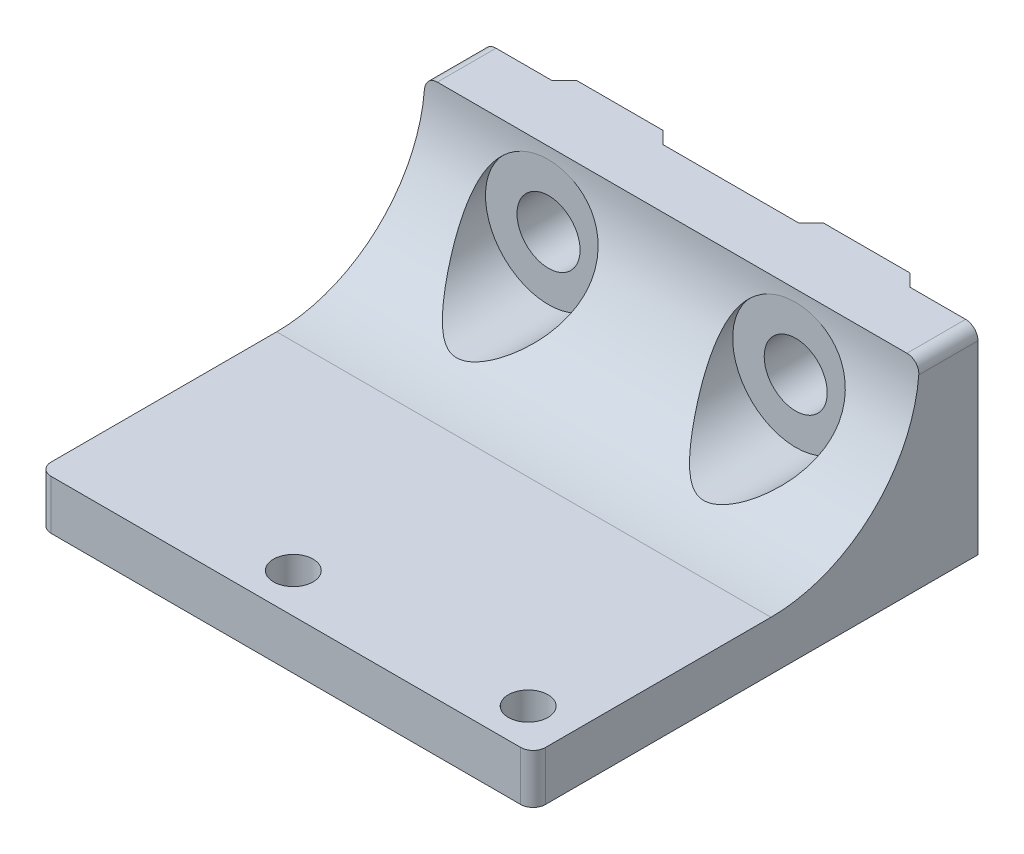
SolidWorks part; units mm, degrees
ref_plane "Front Plane" through (0, 0, 0) normal (0, 0, 1) x (1, 0, 0)
ref_plane "Top Plane" through (0, 0, 0) normal (0, 1, 0) x (1, 0, 0)
ref_plane "Right Plane" through (0, 0, 0) normal (1, 0, 0) x (0, 0, -1)
sketch "Sketch1" plane through (0, 0, 0) normal (0, 1, 0) x (1, 0, 0)
  line L1 (1, 0) -> (39, 0)
  line L2 (0, 1) -> (0, 36)
  line L3 (0, 36) -> (40, 36)
  line L4 (40, 1) -> (40, 36)
  arc A0 (40, 1) -> (39, 0) centre (39, 1) cw
  arc A1 (0, 1) -> (1, 0) centre (1, 1) ccw
  point P9 (0, 0)
  dimension "D3" = 1
  dimension "D1" = 40
  dimension "D2" = 36
extrude "Boss-Extrude1" add sketch "Sketch1" along normal blind 4
sketch "Sketch2" plane through (40, 0, 0) normal (1, 0, 0) x (0, 0, -1)
  line L0 (36, 0) -> (36, 16)
  line L1 (36, 16) -> (31.25, 16)
  line L2 (19.25, 4) -> (19.25, 0)
  line L3 (1, 0) -> (36, 0) construction
  line L4 (19.25, 0) -> (36, 0)
  arc A0 (19.25, 4) -> (31.25, 16) centre (19.25, 16) ccw
  dimension "D3" = 24
  dimension "D1" = 16
  dimension "D2" = 4.75
extrude "Boss-Extrude2" add sketch "Sketch2" against normal through all
sketch "Sketch3" plane through (0, 0, -36) normal (0, 0, -1) x (-1, 0, 0)
  line L0 (0, 16) -> (-40, 16) construction
  line L1 (-34.5, 16) -> (-25.5, 16)
  line L2 (-34.5, 16) -> (-34.5, 0)
  line L3 (-34.5, 0) -> (-25.5, 0)
  line L4 (-25.5, 16) -> (-25.5, 0)
  line L5 (-40, 0) -> (0, 0) construction
  line L6 (-40, 16) -> (-40, 0) construction
  line L7 (-14.5, 16) -> (-5.5, 16)
  line L8 (-14.5, 16) -> (-14.5, 0)
  line L9 (-14.5, 0) -> (-5.5, 0)
  line L10 (-5.5, 16) -> (-5.5, 0)
  dimension "D1" = 9
  dimension "D2" = 9
  dimension "D3" = 11
  dimension "D4" = 5.5
extrude "Boss-Extrude3" add sketch "Sketch3" along normal blind 1
chamfer "Chamfer1" distance 1 angle 45 4 edges at (25.5, 8, -37) (34.5, 8, -37) (14.5, 8, -37) (5.5, 8, -37)
sketch "Sketch4" plane through (0, 0, 0) normal (0, 0, 1) x (1, 0, 0)
  line L0 (0, 16) -> (40, 16) construction
  line L1 (0, 16) -> (0, 4) construction
  line L2 (40, 4) -> (40, 16) construction
  circle A0 centre (10, 10) radius 5.1
  circle A1 centre (30, 10) radius 5.1
  dimension "D1" = 10.2
  dimension "D2" = 10.2
  dimension "D3" = 6
  dimension "D4" = 6
  dimension "D5" = 10
  dimension "D6" = 10
extrude "Cut-Extrude1" cut sketch "Sketch4" against normal blind 31.25
sketch "Sketch5" plane through (0, 0, -37) normal (0, 0, -1) x (-1, 0, 0)
  line L0 (-26.5, 16) -> (-33.5, 16) construction
  line L1 (-6.5, 16) -> (-13.5, 16) construction
  line L2 (-26.5, 0) -> (-26.5, 16) construction
  line L3 (-13.5, 16) -> (-13.5, 0) construction
  circle A0 centre (-30, 10) radius 2.55
  circle A1 centre (-10, 10) radius 2.55
  dimension "D5" = 5.1
  dimension "D6" = 5.1
  dimension "D1" = 6
  dimension "D2" = 6
  dimension "D3" = 3.5
  dimension "D4" = 3.5
extrude "Cut-Extrude2" cut sketch "Sketch5" against normal up to next
fillet "Fillet1" radius 1 2 edges at (0, 16, -33.625) (40, 16, -33.625)
sketch "Sketch6" plane through (0, 4, 0) normal (0, 1, 0) x (1, 0, 0)
  line L0 (40, 1) -> (40, 19.25) construction
  line L2 (1, 0) -> (39, 0) construction
  circle A0 centre (36.4, 3.2) radius 1.6
  circle A1 centre (17.4, 3.2) radius 1.6
  point P8 (0, 0)
  dimension "D1" = 3.2
  dimension "D2" = 3.2
  dimension "D3" = 19
  dimension "D4" = 3.6
  dimension "D5" = 3.2
extrude "Cut-Extrude3" cut sketch "Sketch6" against normal through all
sketch "Sketch7" plane through (0, 0, 0) normal (0, -1, 0) x (1, 0, 0)
  line L0 (40, -1) -> (40, -36) construction
  line L1 (33, -7.75) -> (30, -7.75)
  line L2 (33, -7.75) -> (33, -11.25)
  line L3 (33, -11.25) -> (30, -11.25)
  line L4 (30, -7.75) -> (30, -11.25)
  line L5 (28.25, -7.75) -> (25.25, -7.75)
  line L6 (28.25, -7.75) -> (28.25, -11.25)
  line L7 (28.25, -11.25) -> (25.25, -11.25)
  line L8 (25.25, -7.75) -> (25.25, -11.25)
  line L9 (23.5, -7.75) -> (20.5, -7.75)
  line L10 (23.5, -7.75) -> (23.5, -11.25)
  line L11 (23.5, -11.25) -> (20.5, -11.25)
  line L12 (20.5, -7.75) -> (20.5, -11.25)
  line L13 (1, 0) -> (39, 0) construction
  point P14 (0, 0)
  dimension "D1" = 3
  dimension "D2" = 3
  dimension "D3" = 3
  dimension "D4" = 3.5
  dimension "D5" = 3.5
  dimension "D6" = 3.5
  dimension "D7" = 1.75
  dimension "D8" = 1.75
  dimension "D9" = 7
  dimension "D10" = 7.75
extrude "Cut-Extrude4" cut sketch "Sketch7" against normal blind 1.5
chamfer "Chamfer2" distance 1 angle 45 6 edges at (20.5, 1.5, -9.5) (23.5, 1.5, -9.5) (28.25, 1.5, -9.5) (25.25, 1.5, -9.5) (30, 1.5, -9.5) (33, 1.5, -9.5)
sketch "Sketch8" plane through (0, 0, 0) normal (0, -1, 0) x (1, 0, 0)
  line L0 (0, -36) -> (0, -1) construction
  line L1 (9.5, -3.75) -> (13, -3.75)
  line L2 (9.5, -3.75) -> (9.5, -13.25)
  line L3 (9.5, -13.25) -> (13, -13.25)
  line L4 (13, -3.75) -> (13, -13.25)
  line L6 (1, 0) -> (39, 0) construction
  dimension "D2" = 3.5
  dimension "D1" = 9.5
  dimension "D3" = 9.5
  dimension "D4" = 3.75
extrude "Cut-Extrude5" cut sketch "Sketch8" against normal blind 2
chamfer "Chamfer3" distance 1.5 angle 45 2 edges at (9.5, 2, -8.5) (13, 2, -8.5)
